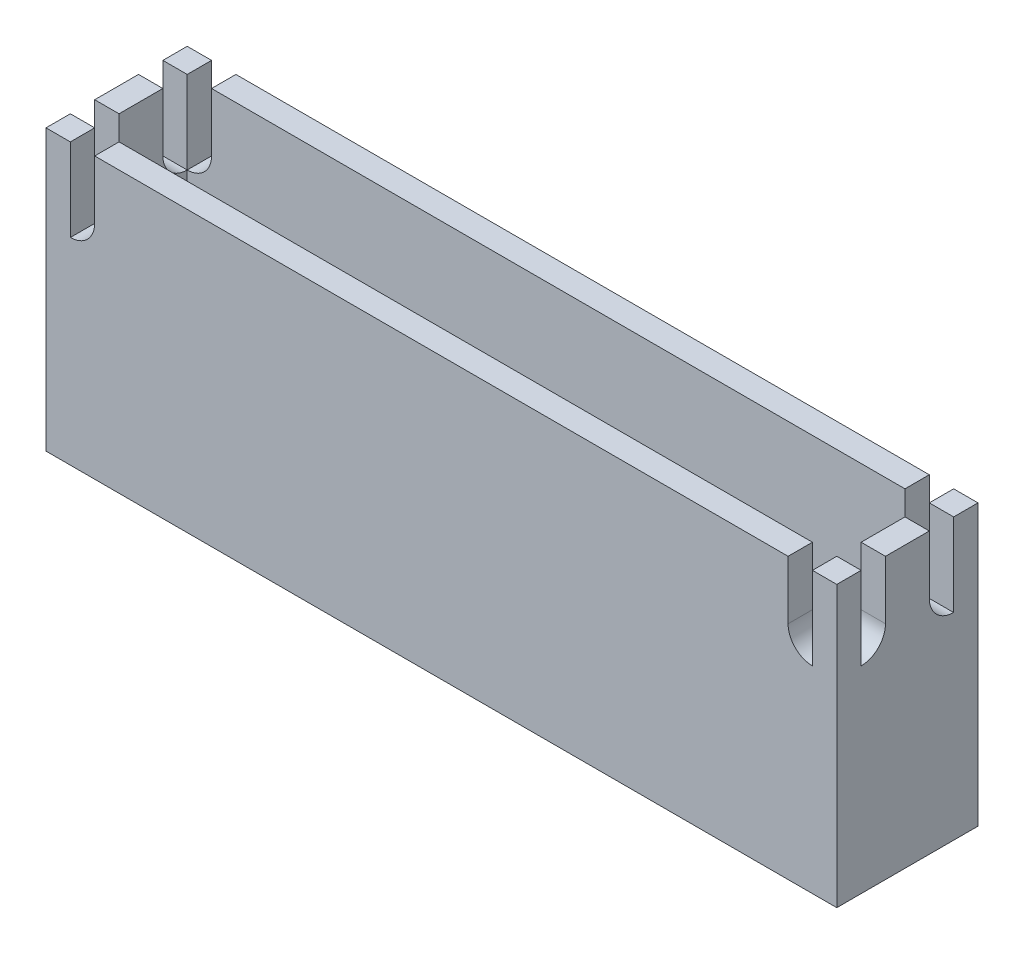
SolidWorks part; units mm, degrees
material "PP Kopolimer"
ref_plane "Front Plane" through (0, 0, 0) normal (0, 0, 1) x (1, 0, 0)
ref_plane "Top Plane" through (0, 0, 0) normal (0, 1, 0) x (1, 0, 0)
ref_plane "Right Plane" through (0, 0, 0) normal (1, 0, 0) x (0, 0, -1)
sketch "Szkic1" plane through (0, 0, 0) normal (0, 1, 0) x (1, 0, 0)
  line L1 (-20.8321, -4.4978) -> (11.6479, -4.4978)
  line L2 (-20.8321, -4.4978) -> (-20.8321, 1.3022)
  line L3 (-20.8321, 1.3022) -> (11.6479, 1.3022)
  line L4 (11.6479, -4.4978) -> (11.6479, 1.3022)
extrude "Dodanie-wyciągnięcie1" add sketch "Szkic1" along normal blind 3.4
sketch "Szkic2" plane through (0, 3.4, 0) normal (0, 1, 0) x (1, 0, 0)
  line L0 (-20.8321, -1.5978) -> (-18.8821, -1.5978) construction
  line L1 (-20.8321, 1.3022) -> (-20.8321, -4.4978) construction
  line L2 (-18.8821, -1.5978) -> (-18.2421, -1.5978) construction
  line L3 (-18.2421, -1.5978) -> (-16.3421, -1.5978) construction
  line L4 (-16.3421, -1.5978) -> (-15.7021, -1.5978) construction
  line L5 (-15.7021, -1.5978) -> (-13.8021, -1.5978) construction
  line L6 (-13.8021, -1.5978) -> (-13.1621, -1.5978) construction
  line L7 (-13.1621, -1.5978) -> (-11.2621, -1.5978) construction
  line L8 (-11.2621, -1.5978) -> (-10.6221, -1.5978) construction
  line L9 (-10.6221, -1.5978) -> (-8.7221, -1.5978) construction
  line L10 (-8.7221, -1.5978) -> (-8.0821, -1.5978) construction
  line L11 (-8.0821, -1.5978) -> (-6.1821, -1.5978) construction
  line L12 (-6.1821, -1.5978) -> (-5.5421, -1.5978) construction
  line L13 (-5.5421, -1.5978) -> (-3.6421, -1.5978) construction
  line L14 (-3.6421, -1.5978) -> (-3.0021, -1.5978) construction
  line L15 (-3.0021, -1.5978) -> (-1.1021, -1.5978) construction
  line L16 (-1.1021, -1.5978) -> (-0.4621, -1.5978) construction
  line L17 (-0.4621, -1.5978) -> (1.4379, -1.5978) construction
  line L18 (1.4379, -1.5978) -> (2.0779, -1.5978) construction
  line L19 (2.0779, -1.5978) -> (3.9779, -1.5978) construction
  line L20 (3.9779, -1.5978) -> (4.6179, -1.5978) construction
  line L21 (4.6179, -1.5978) -> (6.5179, -1.5978) construction
  line L22 (6.5179, -1.5978) -> (7.1579, -1.5978) construction
  line L23 (7.1579, -1.5978) -> (9.0579, -1.5978) construction
  line L24 (9.0579, -1.5978) -> (9.6979, -1.5978) construction
  line L25 (9.6979, -1.5978) -> (11.6479, -1.5978) construction
  line L26 (11.6479, -4.4978) -> (11.6479, 1.3022) construction
  line L28 (-18.8821, -1.9178) -> (-18.2421, -1.9178)
  line L29 (-18.8821, -1.9178) -> (-18.8821, -1.2778)
  line L30 (-18.8821, -1.2778) -> (-18.2421, -1.2778)
  line L31 (-18.2421, -1.9178) -> (-18.2421, -1.2778)
  line L32 (-16.3421, -1.9178) -> (-15.7021, -1.9178)
  line L33 (-16.3421, -1.9178) -> (-16.3421, -1.2778)
  line L34 (-16.3421, -1.2778) -> (-15.7021, -1.2778)
  line L35 (-15.7021, -1.9178) -> (-15.7021, -1.2778)
  line L36 (-13.8021, -1.9178) -> (-13.1621, -1.9178)
  line L37 (-13.8021, -1.9178) -> (-13.8021, -1.2778)
  line L38 (-13.8021, -1.2778) -> (-13.1621, -1.2778)
  line L39 (-13.1621, -1.9178) -> (-13.1621, -1.2778)
  line L40 (-11.2621, -1.9178) -> (-10.6221, -1.9178)
  line L41 (-11.2621, -1.9178) -> (-11.2621, -1.2778)
  line L42 (-11.2621, -1.2778) -> (-10.6221, -1.2778)
  line L43 (-10.6221, -1.9178) -> (-10.6221, -1.2778)
  line L44 (-8.7221, -1.9178) -> (-8.0821, -1.9178)
  line L45 (-8.7221, -1.9178) -> (-8.7221, -1.2778)
  line L46 (-8.7221, -1.2778) -> (-8.0821, -1.2778)
  line L47 (-8.0821, -1.9178) -> (-8.0821, -1.2778)
  line L48 (-6.1821, -1.9178) -> (-5.5421, -1.9178)
  line L49 (-6.1821, -1.9178) -> (-6.1821, -1.2778)
  line L50 (-6.1821, -1.2778) -> (-5.5421, -1.2778)
  line L51 (-5.5421, -1.9178) -> (-5.5421, -1.2778)
  line L52 (-3.6421, -1.9178) -> (-3.0021, -1.9178)
  line L53 (-3.6421, -1.9178) -> (-3.6421, -1.2778)
  line L54 (-3.6421, -1.2778) -> (-3.0021, -1.2778)
  line L55 (-3.0021, -1.9178) -> (-3.0021, -1.2778)
  line L56 (-1.1021, -1.9178) -> (-0.4621, -1.9178)
  line L57 (-1.1021, -1.9178) -> (-1.1021, -1.2778)
  line L58 (-1.1021, -1.2778) -> (-0.4621, -1.2778)
  line L59 (-0.4621, -1.9178) -> (-0.4621, -1.2778)
  line L60 (1.4379, -1.9178) -> (2.0779, -1.9178)
  line L61 (1.4379, -1.9178) -> (1.4379, -1.2778)
  line L62 (1.4379, -1.2778) -> (2.0779, -1.2778)
  line L63 (2.0779, -1.9178) -> (2.0779, -1.2778)
  line L64 (3.9779, -1.9178) -> (4.6179, -1.9178)
  line L65 (3.9779, -1.9178) -> (3.9779, -1.2778)
  line L66 (3.9779, -1.2778) -> (4.6179, -1.2778)
  line L67 (4.6179, -1.9178) -> (4.6179, -1.2778)
  line L68 (6.5179, -1.9178) -> (7.1579, -1.9178)
  line L69 (6.5179, -1.9178) -> (6.5179, -1.2778)
  line L70 (6.5179, -1.2778) -> (7.1579, -1.2778)
  line L71 (7.1579, -1.9178) -> (7.1579, -1.2778)
  line L72 (9.0579, -1.9178) -> (9.6979, -1.9178)
  line L73 (9.0579, -1.9178) -> (9.0579, -1.2778)
  line L74 (9.0579, -1.2778) -> (9.6979, -1.2778)
  line L75 (9.6979, -1.9178) -> (9.6979, -1.2778)
extrude "Wytnij-wyciągnięcie1" cut sketch "Szkic2" against normal blind 3.4
sketch "Szkic3" plane through (0, 3.4, 0) normal (0, 1, 0) x (1, 0, 0)
  line L1 (-20.8321, 1.3022) -> (11.6479, 1.3022)
  line L3 (-19.8321, 0.3022) -> (10.6479, 0.3022)
  line L6 (11.6479, -4.4978) -> (-20.8321, -4.4978)
  line L8 (10.6479, -3.4978) -> (-19.8321, -3.4978)
  line L10 (11.6479, 1.3022) -> (11.6479, -4.4978)
  line L14 (-19.8321, -3.4978) -> (-19.8321, 0.3022)
  line L18 (10.6479, 0.3022) -> (10.6479, -3.4978)
  line L19 (-20.8321, 1.3022) -> (-20.8321, -4.4978)
extrude "Dodanie-wyciągnięcie2" add sketch "Szkic3" along normal blind 8.1
sketch "Szkic4" plane through (0, 11.5, 0) normal (0, 1, 0) x (1, 0, 0)
  line L0 (-20.8321, 1.3022) -> (-20.8321, -4.4978) construction
  line L1 (-19.8321, 0.3022) -> (-18.8321, 0.3022)
  line L2 (-19.8321, 0.3022) -> (-19.8321, 1.3022)
  line L3 (-19.8321, 1.3022) -> (-18.8321, 1.3022)
  line L4 (-18.8321, 0.3022) -> (-18.8321, 1.3022)
  line L5 (-19.8321, 0.3022) -> (-20.8321, 0.3022)
  line L6 (-19.8321, 0.3022) -> (-19.8321, -0.6978)
  line L7 (-19.8321, -0.6978) -> (-20.8321, -0.6978)
  line L8 (-20.8321, 0.3022) -> (-20.8321, -0.6978)
  line L9 (-20.8321, -4.4978) -> (11.6479, -4.4978) construction
  line L10 (-19.8321, -3.4978) -> (-20.8321, -3.4978)
  line L11 (-19.8321, -3.4978) -> (-19.8321, -2.4978)
  line L12 (-19.8321, -2.4978) -> (-20.8321, -2.4978)
  line L13 (-20.8321, -3.4978) -> (-20.8321, -2.4978)
  line L14 (-19.8321, -3.4978) -> (-18.8321, -3.4978)
  line L15 (-19.8321, -3.4978) -> (-19.8321, -4.4978)
  line L16 (-19.8321, -4.4978) -> (-18.8321, -4.4978)
  line L17 (-18.8321, -3.4978) -> (-18.8321, -4.4978)
  line L18 (11.6479, 1.3022) -> (-20.8321, 1.3022) construction
  line L19 (10.6479, 0.3022) -> (9.6479, 0.3022)
  line L20 (10.6479, 0.3022) -> (10.6479, 1.3022)
  line L21 (10.6479, 1.3022) -> (9.6479, 1.3022)
  line L22 (9.6479, 0.3022) -> (9.6479, 1.3022)
  line L23 (11.6479, -4.4978) -> (11.6479, 1.3022) construction
  line L24 (10.6479, 0.3022) -> (11.6479, 0.3022)
  line L25 (10.6479, 0.3022) -> (10.6479, -0.6978)
  line L26 (10.6479, -0.6978) -> (11.6479, -0.6978)
  line L27 (11.6479, 0.3022) -> (11.6479, -0.6978)
  line L29 (10.6479, -3.4978) -> (11.6479, -3.4978)
  line L30 (10.6479, -3.4978) -> (10.6479, -2.4978)
  line L31 (10.6479, -2.4978) -> (11.6479, -2.4978)
  line L32 (11.6479, -3.4978) -> (11.6479, -2.4978)
  line L33 (10.6479, -3.4978) -> (9.6479, -3.4978)
  line L34 (10.6479, -3.4978) -> (10.6479, -4.4978)
  line L35 (10.6479, -4.4978) -> (9.6479, -4.4978)
  line L36 (9.6479, -3.4978) -> (9.6479, -4.4978)
  line M1 (-20.8321, 1.3022) -> (-20.8321, -4.4978)
  line M2 (-20.8321, -4.4978) -> (11.6479, -4.4978)
  line M3 (11.6479, -4.4978) -> (11.6479, 1.3022)
  line M4 (11.6479, 1.3022) -> (-20.8321, 1.3022)
  line M5 (-19.8321, -3.4978) -> (-19.8321, 0.3022)
  line M6 (-19.8321, 0.3022) -> (10.6479, 0.3022)
  line M7 (10.6479, 0.3022) -> (10.6479, -3.4978)
  line M8 (10.6479, -3.4978) -> (-19.8321, -3.4978)
extrude "Wytnij-wyciągnięcie2" cut sketch "Szkic4" against normal blind 3.4 contours L12 L10 M5 M1 | L17 L15 M8 M2 | L7 L5 M5 M1 | L4 L2 M6 M4 | L22 L20 M6 M4 | L26 L24 M7 M3 | L31 L29 M7 M3 | L36 L34 M8 M2 region at (-19.3321, 11.5, -0.8022) region at (-20.3321, 11.5, 0.1978) region at (10.1479, 11.5, -0.8022) region at (-20.3321, 11.5, 2.9978) region at (11.1479, 11.5, 0.1978) region at (-19.3321, 11.5, 3.9978) region at (11.1479, 11.5, 2.9978) region at (10.1479, 11.5, 3.9978)
fillet "Zaokrąglenie1" radius 1 8 edges at (11.1479, 8.1, 2.4978) (11.1479, 8.1, 0.6978) (9.6479, 8.1, -0.8022) (9.6479, 8.1, 3.9978) (-18.8321, 8.1, -0.8022) (-20.3321, 8.1, 0.6978) (-20.3321, 8.1, 2.4978) (-18.8321, 8.1, 3.9978)
